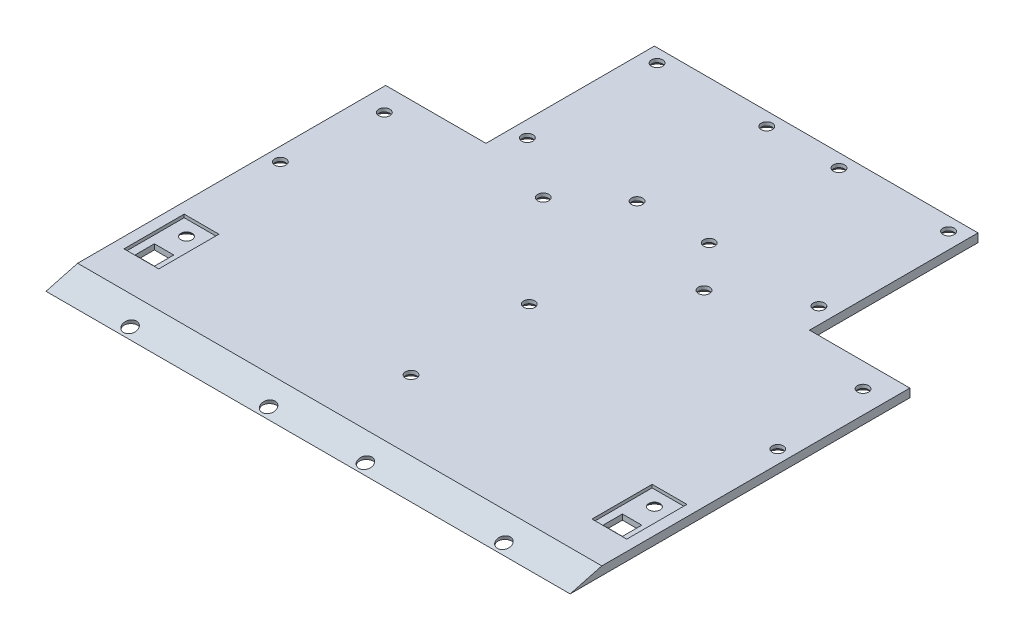
SolidWorks part; units mm, degrees
ref_plane "Alzado" through (0, 0, 0) normal (0, 0, 1) x (1, 0, 0)
ref_plane "Planta" through (0, 0, 0) normal (0, 1, 0) x (1, 0, 0)
ref_plane "Vista lateral" through (0, 0, 0) normal (1, 0, 0) x (0, 0, -1)
sketch "Croquis1" plane through (0, 0, 0) normal (1, 0, 0) x (0, 0, -1)
  line L0 (0, 0) -> (190, 0)
  line L1 (190, 0) -> (190, 3.17)
  line L2 (190, 3.17) -> (11.8306, 3.17)
  line L3 (0, 0) -> (11.8306, 3.17)
  dimension "D1" = 190
  dimension "D2" = 3.17
  dimension "D3" = 165
extrude "Saliente-Extruir1" add sketch "Croquis1" along normal blind 196
sketch "Croquis2" plane through (0, 0, 0) normal (0, -1, 0) x (-1, 0, 0)
  line L0 (0, 190) -> (0, 11.8306) construction
  line L1 (0, 127.0101) -> (-37.5, 127.0101)
  line L2 (0, 127.0101) -> (0, 190)
  line L3 (0, 190) -> (-37.5, 190)
  line L4 (-37.5, 127.0101) -> (-37.5, 190)
  line L5 (0, 127.0101) -> (-37.5, 190) construction
  line L6 (0, 190) -> (-37.5, 127.0101) construction
  line L7 (-196, 127.0101) -> (0, 127.0101) construction
  line L8 (-196, 190) -> (0, 190) construction
  line L9 (-37.5, 131.5) -> (-37.5, 190) construction
  point P4 (-18.75, 158.5051)
extrude "Cortar-Extruir1" cut sketch "Croquis2" against normal up to next
ref_plane "Plano1" through (98, 0, 0) normal (-1, 0, 0) x (0, 0, 1)
mirror "Simetría1" about plane through (98, 0, 0) normal (-1, 0, 0) of "Cortar-Extruir1"
sketch "Croquis3" plane through (0, 3.17, 0) normal (0, 1, 0) x (1, 0, 0)
  line L0 (196, 0) -> (0, 0) construction
  line L1 (4, 47.66) -> (17, 47.66)
  line L2 (4, 47.66) -> (4, 25.16)
  line L3 (4, 25.16) -> (17, 25.16)
  line L4 (17, 47.66) -> (17, 25.16)
  line L5 (4, 47.66) -> (17, 25.16) construction
  line L6 (4, 25.16) -> (17, 47.66) construction
  line L7 (0, 127.0101) -> (0, 11.8306) construction
  point P4 (10.5, 36.41)
  dimension "D1" = 25.16
  dimension "D2" = 22.5
  dimension "D3" = 13
  dimension "D4" = 4
extrude "Cortar-Extruir2" cut sketch "Croquis3" against normal blind 1.17
sketch "Croquis4" plane through (0, 2, 0) normal (0, 1, 0) x (1, 0, 0)
  line L0 (10.5, 25.16) -> (10.5, 26.41) construction
  line L1 (4, 25.16) -> (17, 25.16) construction
  line L2 (4, 26.41) -> (17, 26.41) construction
  line L3 (4, 47.66) -> (4, 25.16) construction
  line L4 (17, 25.16) -> (17, 47.66) construction
  line L5 (10.5, 26.41) -> (10.5, 33.66) construction
  line L6 (10.5, 30.035) -> (6.875, 30.035) construction
  line L7 (10.5, 30.035) -> (14.125, 30.035) construction
  line L8 (6.875, 30.035) -> (6.875, 26.41) construction
  line L9 (14.125, 30.035) -> (14.125, 33.66) construction
  dimension "D1" = 1.25
  dimension "D2" = 7.25
  dimension "D3" = 3.625
  dimension "D4" = 3.625
sketch "Croquis5" plane through (0, 2, 0) normal (0, 1, 0) x (1, 0, 0)
  line L1 (6.875, 26.41) -> (14.125, 26.41)
  line L2 (6.875, 26.41) -> (6.875, 33.66)
  line L3 (6.875, 33.66) -> (14.125, 33.66)
  line L4 (14.125, 26.41) -> (14.125, 33.66)
  line L5 (6.875, 26.41) -> (14.125, 33.66) construction
  line L6 (6.875, 33.66) -> (14.125, 26.41) construction
  point P4 (10.5, 30.035)
extrude "Cortar-Extruir3" cut sketch "Croquis5" against normal up to next
sketch "Croquis6" plane through (0, 2, 0) normal (0, 1, 0) x (1, 0, 0)
  line L0 (10.5, 47.66) -> (10.5, 46.41) construction
  line L1 (17, 47.66) -> (4, 47.66) construction
  line L2 (10.5, 46.41) -> (17, 46.41) construction
  line L3 (17, 25.16) -> (17, 47.66) construction
  line L4 (17, 46.41) -> (4, 46.41) construction
  line L5 (4, 47.66) -> (4, 25.16) construction
  circle A0 centre (10.5, 42.01) radius 1.6
  dimension "D2" = 3.2
  dimension "D1" = 1.25
  dimension "D3" = 4.4
extrude "Cortar-Extruir4" cut sketch "Croquis6" against normal up to next
mirror "Simetría2" about plane through (98, 0, 0) normal (-1, 0, 0) of "Cortar-Extruir2", "Cortar-Extruir4", "Cortar-Extruir3"
sketch "Sketch1" plane through (0, 3.17, 0) normal (0, 1, 0) x (1, 0, 0)
  circle A0 centre (8.5, 118.0101) radius 1.585
  circle A1 centre (187.5, 118.0101) radius 1.585
extrude "Cut-Extrude1" cut sketch "Sketch1" against normal up to next
sketch "Sketch2" plane through (0, 3.17, 0) normal (0, 1, 0) x (1, 0, 0)
  circle A0 centre (98.5, 38.0101) radius 1.585
extrude "Cut-Extrude2" cut sketch "Sketch2" against normal up to next
sketch "Sketch3" plane through (0, 3.17, 0) normal (0, 1, 0) x (1, 0, 0)
  circle A0 centre (43.5, 185) radius 1.5799
  circle A1 centre (84.5, 185) radius 1.585
  circle A2 centre (152.5, 185) radius 1.585
  circle A3 centre (111.5, 185) radius 1.585
  circle A4 centre (111.5, 136.5) radius 1.585
  circle A5 centre (152.5, 136.5) radius 1.585
  circle A6 centre (84.5, 136.5) radius 1.585
  circle A7 centre (43.5, 136.5) radius 1.585
extrude "Cut-Extrude3" cut sketch "Sketch3" against normal up to next
sketch "Sketch4" plane through (0, 3.17, 0) normal (0, 1, 0) x (1, 0, 0)
  circle A0 centre (65.7764, 120.1669) radius 1.6
  circle A1 centre (125.8764, 120.1669) radius 1.6
extrude "Cut-Extrude4" cut sketch "Sketch4" against normal blind 4.9
hole_wizard "Avellanado para tornillo con cabeza avellanada en cruz de M3.51" positions "3DSketch1" profile "Sketch5" countersink size "M3.5" standard "AS"
sketch3d "3DSketch1"
  line L0 (187.5, 0, -118.0101) -> (187.5, 3.17, -118.0101) construction
  line L1 (152.5, 0, -136.5) -> (152.5, 3.17, -136.5) construction
  line L2 (125.8764, 0, -120.1669) -> (125.8764, 3.17, -120.1669) construction
  line L3 (111.5, 0, -136.5) -> (111.5, 3.17, -136.5) construction
  line L4 (84.5, 0, -136.5) -> (84.5, 3.17, -136.5) construction
  line L5 (65.7764, 0, -120.1669) -> (65.7764, 3.17, -120.1669) construction
  line L6 (43.5, 0, -136.5) -> (43.5, 3.17, -136.5) construction
  line L7 (8.5, 0, -118.0101) -> (8.5, 3.17, -118.0101) construction
  line L8 (43.5, 0, -185) -> (43.5, 3.17, -185) construction
  line L9 (84.5, 0, -185) -> (84.5, 3.17, -185) construction
  line L10 (111.5, 0, -185) -> (111.5, 3.17, -185) construction
  line L11 (152.5, 0, -185) -> (152.5, 3.17, -185) construction
  line L12 (10.5, 0, -42.01) -> (10.5, 2, -42.01) construction
  line L13 (98.5, 0, -38.0101) -> (98.5, 3.17, -38.0101) construction
  line L14 (185.5, 0, -42.01) -> (185.5, 2, -42.01) construction
  point P0 (187.5, 0, -118.0101)
  point P4 (152.5, 0, -136.5)
  point P8 (125.8764, 0, -120.1669)
  point P12 (111.5, 0, -136.5)
  point P16 (84.5, 0, -136.5)
  point P20 (65.7764, 0, -120.1669)
  point P24 (43.5, 0, -136.5)
  point P28 (8.5, 0, -118.0101)
  point P32 (43.5, 0, -185)
  point P36 (84.5, 0, -185)
  point P40 (111.5, 0, -185)
  point P44 (152.5, 0, -185)
  point P48 (10.5, 0, -42.01)
  point P52 (98.5, 0, -38.0101)
  point P56 (185.5, 0, -42.01)
sketch "Sketch5" plane through (187.5, 0, -118.0101) normal (1, 0, 0) x (0, 0, -1)
  line L0 (0, 0) -> (0, 11.2618)
  line L1 (0, 11.2618) -> (2.1, 10)
  line L2 (2.1, 10) -> (2.1, 1.8348)
  line L3 (2.1, 1.8348) -> (4, 0)
  line L5 (4, 0) -> (0, 0)
  line L6 (-2.1, 1.8348) -> (-4, 0) construction
  line L10 (0, 11.2618) -> (-2.1, 10) construction
  line L11 (0, -6.35) -> (0, 107.95) construction
  dimension "Diámetro de taladro" = 4.2
  dimension "Profundidad de taladro" = 10
  dimension "Ángulo de avellanado cercano" = 8
  dimension "Ángulo de avellanado lejano" = 92
  dimension "Ángulo de perforador" = 118
sketch "Sketch6" plane through (0, 3.17, 0) normal (0, 1, 0) x (1, 0, 0)
  circle A0 centre (191.0671, 82.5578) radius 1.585
  circle A1 centre (97.6819, 83.0385) radius 1.585
  circle A2 centre (5.0671, 82.5578) radius 1.585
extrude "Cut-Extrude5" cut sketch "Sketch6" against normal blind 10
sketch "Sketch8" plane through (0, 0, 0) normal (0, 0.9659, 0.2588) x (1, 0, 0)
  circle A0 centre (28.1, 3.4495) radius 2.5
  circle A1 centre (79.9, 3.4495) radius 2.5
  circle A2 centre (116.1, 3.4495) radius 2.5
  circle A3 centre (167.9, 3.4495) radius 2.5
extrude "Cut-Extrude6" cut sketch "Sketch8" against normal blind 10
hole_wizard "Avellanado para tornillo con cabeza avellanada en cruz de M3.53" positions "3DSketch3" profile "Sketch10" countersink size "M3.5" standard "AS"
sketch3d "3DSketch3"
  line L0 (97.6819, 0, -83.0385) -> (97.6819, 3.17, -83.0385) construction
  line L1 (5.0671, 0, -82.5578) -> (5.0671, 3.17, -82.5578) construction
  line L2 (191.0671, 0, -82.5578) -> (191.0671, 3.17, -82.5578) construction
  point P0 (97.6819, 0, -83.0385)
  point P4 (5.0671, 0, -82.5578)
  point P8 (191.0671, 0, -82.5578)
sketch "Sketch10" plane through (97.6819, 0, -83.0385) normal (1, 0, 0) x (0, 0, -1)
  line L0 (0, 0) -> (0, 11.2618)
  line L1 (0, 11.2618) -> (2.1, 10)
  line L2 (2.1, 10) -> (2.1, 1.8348)
  line L3 (2.1, 1.8348) -> (4, 0)
  line L5 (4, 0) -> (0, 0)
  line L6 (-2.1, 1.8348) -> (-4, 0) construction
  line L10 (0, 11.2618) -> (-2.1, 10) construction
  line L11 (0, -6.35) -> (0, 107.95) construction
  dimension "Diámetro de taladro" = 4.2
  dimension "Profundidad de taladro" = 10
  dimension "Ángulo de avellanado cercano" = 8
  dimension "Ángulo de avellanado lejano" = 92
  dimension "Ángulo de perforador" = 118
